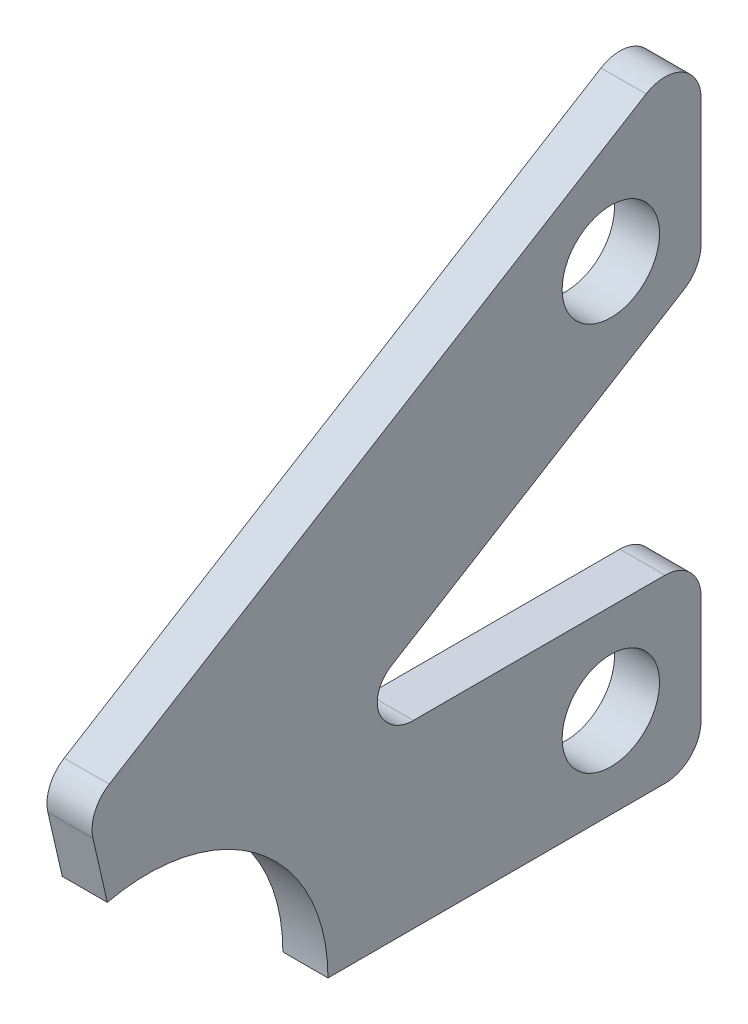
SolidWorks part; units mm, degrees
material "AISI 4130 Steel, annealed at 865C"
ref_plane "Front Plane" through (0, 0, 0) normal (0, 0, 1) x (1, 0, 0)
ref_plane "Top Plane" through (0, 0, 0) normal (0, 1, 0) x (1, 0, 0)
ref_plane "Right Plane" through (0, 0, 0) normal (1, 0, 0) x (0, 0, -1)
sketch "Sketch2" plane through (-112.555, 0, -573.5897) normal (-1, 0, 0) x (0, 0.6231, 0.7821)
  line L0 (845.7718, 136.9996) -> (864.3306, 122.2137)
  line L1 (871.0899, 172.8543) -> (811.2713, 97.7721) construction
  line L2 (864.3306, 122.2137) -> (884.1965, 122.2137) construction
  line L3 (884.1965, 122.2137) -> (887.7358, 125.0335)
  line L4 (853.6855, 146.9326) -> (867.5451, 135.8905)
  line L5 (888.541, 127.8859) -> (873.4237, 169.576)
  line L6 (871.3239, 138.1115) -> (863.0777, 160.8527)
  line L7 (845.3679, 140.569) -> (850.1161, 146.5287)
  line L8 (863.479, 163.3013) -> (869.0493, 170.2929)
  line L9 (852.7085, 139.592) -> (869.7744, 161.0125) construction
  circle A0 centre (874.2635, 114.3) radius 12.7 construction
  arc A1 (864.3306, 122.2137) -> (884.1965, 122.2137) centre (874.2635, 114.3) cw
  arc A2 (887.7358, 125.0335) -> (888.541, 127.8859) centre (886.1531, 127.0201) ccw
  circle A3 centre (852.7085, 139.592) radius 3.429
  circle A4 centre (869.7744, 161.0125) radius 3.429
  arc A6 (869.8308, 135.4301) -> (869.6684, 135.3953) centre (874.2635, 114.3) ccw
  arc A7 (845.7718, 136.9996) -> (845.3679, 140.569) centre (847.3545, 138.9862) cw
  arc A8 (853.6855, 146.9326) -> (850.1161, 146.5287) centre (852.1027, 144.946) ccw
  arc A9 (869.0493, 170.2929) -> (873.4237, 169.576) centre (871.0358, 168.7102) cw
  arc A10 (863.0777, 160.8527) -> (863.479, 163.3013) centre (865.4656, 161.7186) cw
  arc A11 (867.5451, 135.8905) -> (869.6684, 135.3953) centre (869.1278, 137.8771) ccw
  arc A12 (871.3239, 138.1115) -> (869.8308, 135.4301) centre (869.4136, 137.4188) cw
  point P17 (889.163, 126.1705)
  point P25 (843.7852, 138.5824)
  point P28 (851.6989, 148.5153)
  point P31 (871.8768, 173.842)
  point P34 (862.593, 162.1893)
  dimension "D5" = 2.54
  dimension "D6" = 6.858
  dimension "D10" = 6.858
  dimension "D9" = 2.54
  dimension "D4" = 8.89
  dimension "D12" = 2.54
  dimension "D13" = 2.54
  dimension "D14" = 2.54
  dimension "D15" = 2.54
  dimension "D16" = 2.032
  dimension "D1" = 12.7
  dimension "D2" = 12.7
  dimension "D3" = 6.35
  dimension "D7" = 6.35
  dimension "D8" = 6.35
  dimension "D11" = 6.35
extrude "Boss-Extrude1" add sketch "Sketch2" along normal blind 3.175
ref_plane "Plane1" through (0, 375.1306, -298.8699) normal (0, -0.7821, 0.6231) x (-1, 0, 0)
